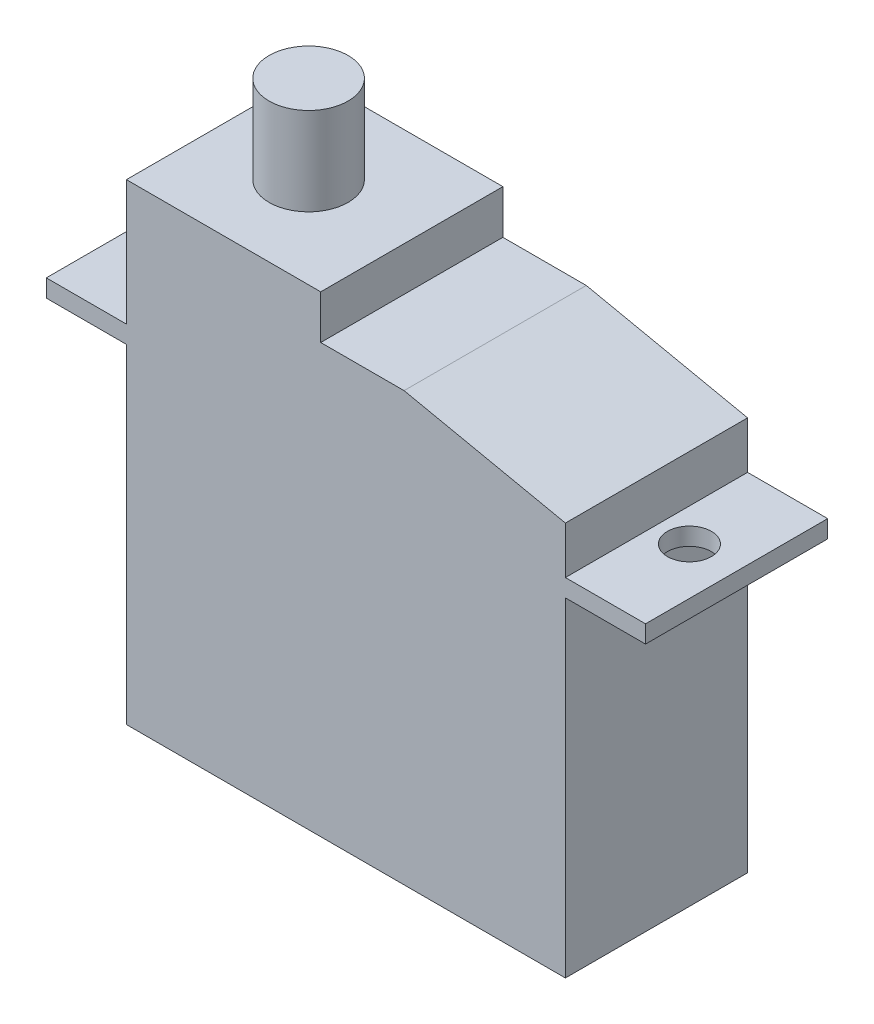
SolidWorks part; units mm, degrees
ref_plane "前视基准面" through (0, 0, 0) normal (0, 0, 1) x (1, 0, 0)
ref_plane "上视基准面" through (0, 0, 0) normal (0, 1, 0) x (1, 0, 0)
ref_plane "右视基准面" through (0, 0, 0) normal (1, 0, 0) x (0, 0, -1)
sketch "草图1" plane through (0, 0, 0) normal (0, 0, 1) x (1, 0, 0)
  line L0 (12.6497, 19.5) -> (20, 17.9509)
  line L1 (0, 0) -> (20, 0)
  line L2 (0, 0) -> (0, 16.3363)
  line L3 (8.8523, 19.5) -> (12.6497, 19.5)
  line L4 (20, 0) -> (20, 17.9509)
  line L7 (0, 16.3363) -> (0, 21.5)
  line L8 (0, 21.5) -> (8.8523, 21.5)
  line L9 (8.8523, 19.5) -> (8.8523, 21.5)
  dimension "D1" = 20
  dimension "D2" = 19.5
  dimension "D3" = 2
extrude "凸台-拉伸1" add sketch "草图1" along normal mid plane 8.3
sketch "草图2" plane through (0, 0, 4.15) normal (0, 0, 1) x (1, 0, 0)
  line L0 (0, 0) -> (20, 0) construction
  line L1 (-3.65, 15) -> (23.65, 15)
  line L2 (-3.65, 15) -> (-3.65, 15.8)
  line L3 (-3.65, 15.8) -> (23.65, 15.8)
  line L4 (23.65, 15) -> (23.65, 15.8)
  line L5 (20, 0) -> (20, 17.9509) construction
  dimension "D1" = 27.3
  dimension "D2" = 0.8
  dimension "D3" = 15
  dimension "D4" = 3.65
extrude "凸台-拉伸2" add sketch "草图2" against normal blind 8.3
sketch "草图3" plane through (0, 15.8, 0) normal (0, 1, 0) x (1, 0, 0)
  line L0 (-3.65, 4.15) -> (-3.65, -4.15) construction
  circle A0 centre (-1.5, 0) radius 1
  circle A1 centre (21.5, 0) radius 1
  dimension "D1" = 23
  dimension "D2" = 2.15
extrude "切除-拉伸1" cut sketch "草图3" against normal up to next
sketch "草图4" plane through (0, 21.5, 0) normal (0, 1, 0) x (1, 0, 0)
  line L0 (0, -4.15) -> (0, 4.15) construction
  line L1 (8.8523, -4.15) -> (0, -4.15) construction
  circle A0 centre (4.15, 0) radius 1.8
  dimension "D1" = 4.15
  dimension "D2" = 3.6
  dimension "D3" = 4.15
extrude "凸台-拉伸3" add sketch "草图4" along normal blind 4
ref_axis "Axis1" through (4.15, 25.5, 0) along (0, -1, 0)
